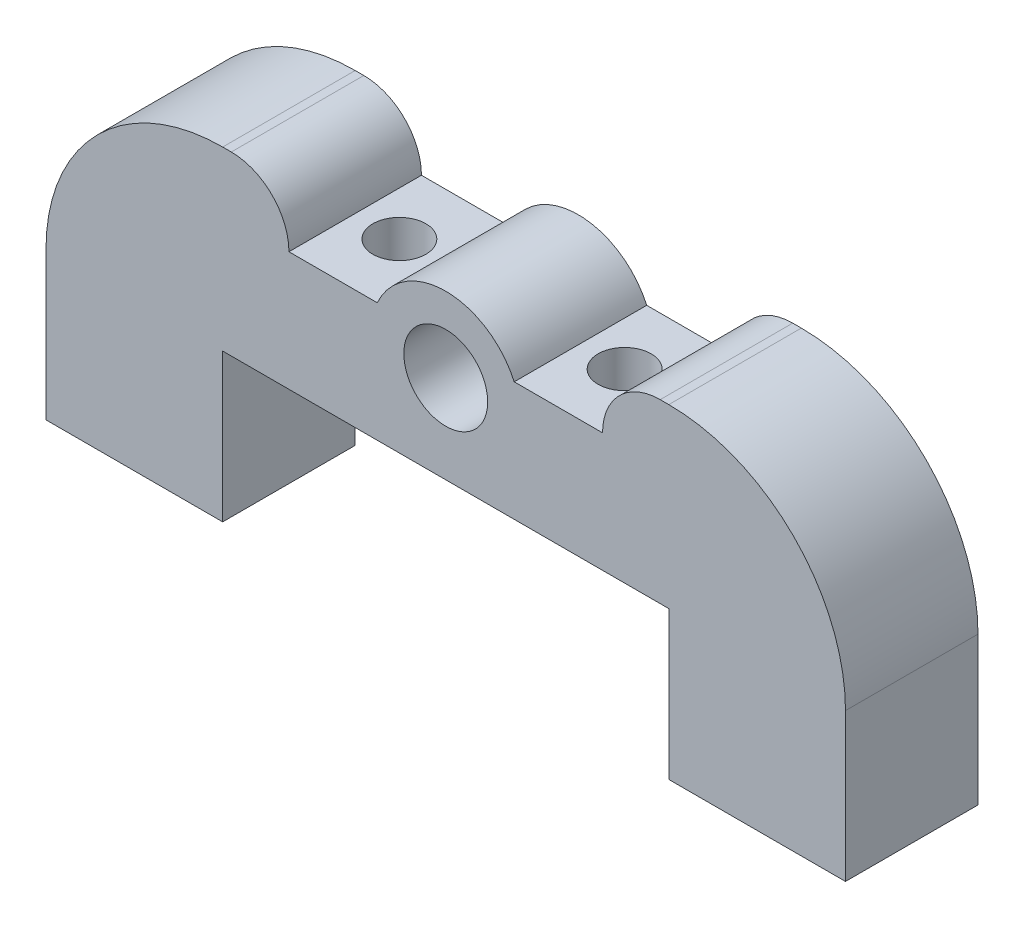
SolidWorks part; units mm, degrees
ref_plane "Front Plane" through (0, 0, 0) normal (0, 0, 1) x (1, 0, 0)
ref_plane "Top Plane" through (0, 0, 0) normal (0, 1, 0) x (1, 0, 0)
ref_plane "Right Plane" through (0, 0, 0) normal (1, 0, 0) x (0, 0, -1)
sketch "Sketch1" plane through (0, 0, 0) normal (0, 0, 1) x (1, 0, 0)
  line L0 (-8, 0) -> (-8, 6.7)
  line L2 (0, 0) -> (0, 6.7)
  line L3 (0, 6.7) -> (20.2, 6.7)
  line L4 (20.2, 0) -> (20.2, 6.7)
  line L5 (0, 14.7) -> (20.2, 14.7)
  line L6 (28.2, 0) -> (28.2, 6.7)
  line L8 (-8, -8) -> (-8, 14.7) construction
  line L9 (-8, -8) -> (28.2, -8) construction
  line L10 (28.2, -8) -> (28.2, 14.7) construction
  line L11 (-8, 14.7) -> (28.2, 14.7) construction
  line L12 (-8, 0) -> (0, 0)
  line L13 (20.2, 0) -> (28.2, 0)
  line L14 (0, 0) -> (20.2, 0) construction
  arc A2 (20.2, 14.7) -> (28.2, 6.7) centre (20.2, 6.7) cw
  arc A3 (-8, 6.7) -> (0, 14.7) centre (0, 6.7) cw
  point P1 (0, 0)
  point P2 (0, 0)
  point P4 (-0.1406, -0.0162)
  point P10 (0.0194, 0)
  point P11 (0, 0)
  point P13 (0, 0)
  point P14 (0, 0)
  dimension "D4" = 8
  dimension "D1" = 6.7
  dimension "D2" = 20.2
extrude "Boss-Extrude1" add sketch "Sketch1" along normal blind 6 contours A3 L0 L12 L2 L3 L4 L13 L6 A2 L5 region at (10.1, 8.402, 0)
hole_wizard "#6 Clearance Hole1" positions "Sketch2" profile "Sketch3" hole size "#6" standard "ANSI Inch" end condition through all
sketch "Sketch2" plane through (0, 0, 6) normal (0, 0, 1) x (1, 0, 0)
  line L0 (0, 6.7) -> (20.2, 6.7) construction
  line L1 (0, 14.7) -> (20.2, 14.7) construction
  point P0 (10.1, 10.7)
  point P5 (0, 0)
  point P8 (10.1, 14.7)
  dimension "D1" = 4
sketch "Sketch3" plane through (10.1, 10.7, 6) normal (1, 0, 0) x (0, -1, 0)
  line L0 (0, 0) -> (0, 6)
  line L1 (0, 6) -> (1.8986, 6)
  line L2 (1.8986, 6) -> (1.8986, 0)
  line L5 (1.8986, 0) -> (0, 0)
  line L11 (0, -6.35) -> (0, 107.95) construction
  dimension "Thru Hole Dia." = 3.7973
  dimension "Thru Hole Depth" = 6
sketch "Sketch5" plane through (0, 0, 6) normal (0, 0, 1) x (1, 0, 0)
  line L0 (0, 14.7) -> (20.2, 14.7) construction
  line L1 (3, 14.7) -> (7, 14.7)
  line L2 (3, 14.7) -> (3, 12.0931)
  line L3 (3, 12.0931) -> (7, 12.0931)
  line L5 (10.1, 10.7) -> (10.1, 6.6284) construction
  line L6 (17.2, 12.0931) -> (13.2, 12.0931)
  line L8 (17.2, 14.7) -> (13.2, 14.7)
  line L9 (17.2, 14.7) -> (17.2, 12.0931)
  line L10 (7, 14.7) -> (13.2, 14.7)
  circle A2 centre (10.1, 10.7) radius 3.3986
  circle A3 centre (10.1, 10.7) radius 3.3987
  point P14 (0, 0)
  line M16 (20.2, 14.7) -> (0, 14.7)
  dimension "D1" = 4
  dimension "D2" = 3
  dimension "D4" = 1.5
extrude "Cut-Extrude1" cut sketch "Sketch5" against normal up to next contours A3 L6 L9 L2 L3 M16 region at (5, 14.5556, 6)
fillet "Fillet1" radius 2.61 2 edges at (17.2, 14.7, 3) (3, 14.7, 3)
hole_wizard "M2 Clearance Hole1" positions "Sketch6" profile "Sketch7" hole size "M2" standard "ANSI Metric" end condition through all
sketch "Sketch6" plane through (0, 12.0931, 0) normal (0, 1, 0) x (1, 0, 0)
  line L2 (5, 0) -> (5, -6) construction
  line L3 (7, 0) -> (3, 0) construction
  line L4 (3, -6) -> (7, -6) construction
  line L7 (7, -3) -> (3, -3) construction
  line L8 (7, 0) -> (7, -6) construction
  line L11 (3, 0) -> (3, -6) construction
  line L12 (15.2, 0) -> (15.2, -6) construction
  line L13 (13.2, 0) -> (17.2, 0) construction
  line L14 (17.2, -6) -> (13.2, -6) construction
  point P0 (5, -3)
  point P2 (15.2, -3)
  point P47 (15.2, -3)
sketch "Sketch7" plane through (5, 12.0931, 3) normal (1, 0, 0) x (0, 0, 1)
  line L0 (0, 0) -> (0, 12.0931)
  line L1 (0, 12.0931) -> (1.2, 12.0931)
  line L2 (1.2, 12.0931) -> (1.2, 0)
  line L5 (1.2, 0) -> (0, 0)
  line L11 (0, -6.35) -> (0, 107.95) construction
  dimension "Thru Hole Dia." = 2.4
  dimension "Thru Hole Depth" = 12.0931
